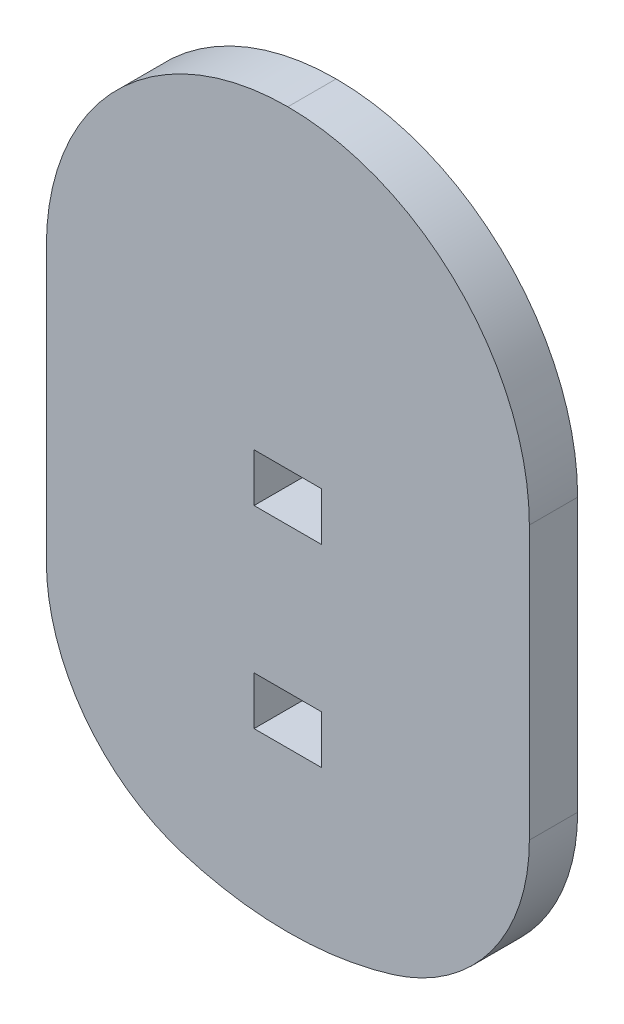
SolidWorks part; units mm, degrees
material "Acrylic (Medium-high impact)"
ref_plane "Front Plane" through (0, 0, 0) normal (0, 0, 1) x (1, 0, 0)
ref_plane "Top Plane" through (0, 0, 0) normal (0, 1, 0) x (1, 0, 0)
ref_plane "Right Plane" through (0, 0, 0) normal (1, 0, 0) x (0, 0, -1)
sketch "Sketch1" plane through (0, 0, 0) normal (0, 0, 1) x (1, 0, 0)
  circle A0 centre (0, 0) radius 37
  point P0 (0, 0)
  dimension "D1" = 74
extrude "Boss-Extrude1" add sketch "Sketch1" along normal blind 5
sketch "Sketch10" plane through (0, 0, 5) normal (0, 0, 1) x (1, 0, 0)
  line L0 (-25, 27.2764) -> (-25, -27.2764)
  line L2 (25, -27.2764) -> (25, 27.2764)
  circle A0 centre (0, 0) radius 37 construction
  arc A1 (-25, 27.2764) -> (-25, -27.2764) centre (0, 0) ccw
  circle A2 centre (0, 0) radius 37
  arc A3 (25, -27.2764) -> (25, 27.2764) centre (0, 0) ccw
  dimension "D2" = 25
  dimension "D3" = 50
  dimension "D1" = 0
extrude "Cut-Extrude3" cut sketch "Sketch10" against normal blind 10
fillet "Fillet1" radius 25 2 edges at (-25, 27.2764, 2.5) (25, 27.2764, 2.5)
fillet "Fillet2" radius 20 2 edges at (-25, -27.2764, 2.5) (25, -27.2764, 2.5)
sketch "Sketch11" plane through (0, 0, 5) normal (0, 0, 1) x (1, 0, 0)
  line L1 (-3.5, 4.5) -> (3.5, 4.5)
  line L2 (-3.5, 4.5) -> (-3.5, -0.5)
  line L3 (-3.5, -0.5) -> (3.5, -0.5)
  line L4 (3.5, 4.5) -> (3.5, -0.5)
  line L5 (-3.5, 4.5) -> (3.5, -0.5) construction
  line L6 (-3.5, -0.5) -> (3.5, 4.5) construction
  line L7 (-3.5, -15.5) -> (3.5, -15.5)
  line L8 (-3.5, -15.5) -> (-3.5, -20.5)
  line L9 (-3.5, -20.5) -> (3.5, -20.5)
  line L10 (3.5, -15.5) -> (3.5, -20.5)
  line L11 (-3.5, -15.5) -> (3.5, -20.5) construction
  line L12 (-3.5, -20.5) -> (3.5, -15.5) construction
  point P0 (0, 2)
  point P5 (0, -18)
  point P14 (0, -0.5)
  dimension "D1" = 32.5
  dimension "D2" = 25
  dimension "D3" = 7
  dimension "D4" = 5
extrude "Cut-Extrude4" cut sketch "Sketch11" against normal blind 10
sketch "Sketch4" plane through (0, 0, 5) normal (0, 0, 1) x (1, 0, 0)
  line L1 (-11, 4.5) -> (11, 4.5)
  line L2 (-11, 4.5) -> (-11, -0.5)
  line L3 (-11, -0.5) -> (11, -0.5)
  line L4 (11, 4.5) -> (11, -0.5)
  line L5 (-11, 4.5) -> (11, -0.5) construction
  line L6 (-11, -0.5) -> (11, 4.5) construction
  point P0 (0, 2)
  dimension "D1" = 22
  dimension "D2" = 5
  dimension "D3" = 2
extrude "Boss-Extrude2" [suppressed] add sketch "Sketch4" along normal blind 35
sketch "Sketch5" [suppressed] plane through (0, 4.5, 0) normal (0, 1, 0) x (1, 0, 0)
  line L1 (-6, -11) -> (6, -11)
  line L2 (-6, -11) -> (-6, -34)
  line L3 (-6, -34) -> (6, -34)
  line L4 (6, -11) -> (6, -34)
  line L5 (-6, -11) -> (6, -34) construction
  line L6 (-6, -34) -> (6, -11) construction
  line L7 (-11, -40) -> (-11, -5) construction
  line L8 (11, -40) -> (-11, -40) construction
  point P0 (0, -22.5)
  point P10 (-11, -22.5)
  point P12 (0, -40)
  dimension "D1" = 12
  dimension "D2" = 23
extrude "Cut-Extrude1" [suppressed] cut sketch "Sketch5" against normal blind 5
sketch "Sketch6" [suppressed] plane through (0, 4.5, 0) normal (0, 1, 0) x (1, 0, 0)
  line L0 (0, -8) -> (0, -37) construction
  line L1 (-6, -11) -> (-6, -34) construction
  line L2 (-6, -34) -> (6, -34) construction
  circle A0 centre (0, -8) radius 1.25
  circle A1 centre (0, -37) radius 1.25
  point P4 (0, -22.5)
  point P7 (-6, -22.5)
  point P10 (0, -34)
  dimension "D1" = 2.5
  dimension "D2" = 29
extrude "Cut-Extrude2" [suppressed] cut sketch "Sketch6" against normal blind 5
sketch "Sketch7" [suppressed] plane through (0, 0, 40) normal (0, 0, 1) x (1, 0, 0)
  line L0 (11, -0.5) -> (11, 4.5) construction
  line L1 (-11, 4.5) -> (11, 4.5)
  line L2 (-11, 4.5) -> (-11, -15.5)
  line L3 (-11, -15.5) -> (11, -15.5)
  line L4 (11, 4.5) -> (11, -15.5)
  line L5 (11, -0.5) -> (11, 4.5) construction
  dimension "D1" = 20
extrude "Boss-Extrude3" [suppressed] add sketch "Sketch7" along normal blind 5
sketch "Sketch8" [suppressed] plane through (0, -15.5, 0) normal (0, -1, 0) x (1, 0, 0)
  line L1 (-11, 45) -> (11, 45)
  line L2 (-11, 45) -> (-11, 5)
  line L3 (-11, 5) -> (11, 5)
  line L4 (11, 45) -> (11, 5)
extrude "Boss-Extrude4" [suppressed] add sketch "Sketch8" along normal blind 5
sketch "Sketch9" [suppressed] plane through (0, -20.5, 0) normal (0, -1, 0) x (1, 0, 0)
  line L0 (-11, 5) -> (11, 5) construction
  circle A0 centre (0, 27.5) radius 3.75
  dimension "D1" = 7.5
  dimension "D2" = 22.5
extrude "Boss-Extrude5" [suppressed] add sketch "Sketch9" along normal blind 7
fillet "Fillet3" [suppressed] radius 0.5
